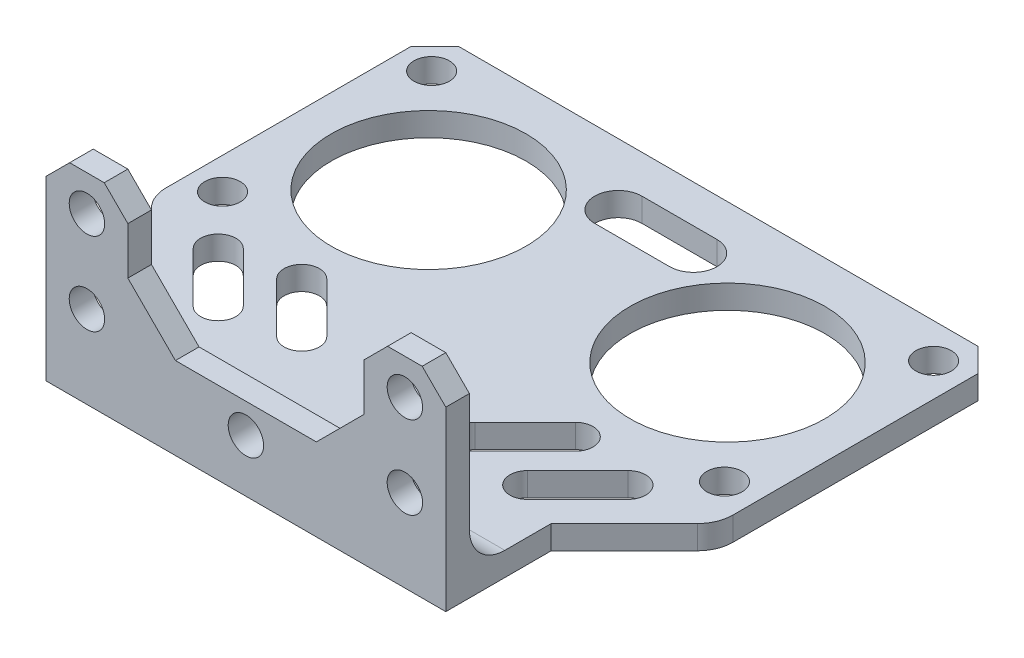
SolidWorks part; units mm, degrees
ref_plane "Front" through (0, 0, 0) normal (0, 0, 1) x (1, 0, 0)
ref_plane "Top" through (0, 0, 0) normal (0, 1, 0) x (1, 0, 0)
ref_plane "Right" through (0, 0, 0) normal (1, 0, 0) x (0, 0, -1)
sketch "Sketch1" plane through (0, 0, 0) normal (0, 1, 0) x (1, 0, 0)
  line L0 (-24, -12) -> (-16.9289, -19.0711)
  line L2 (-24, -12) -> (-24, 12)
  line L3 (-24, 12) -> (24, 12)
  line L4 (24, -12) -> (24, 12)
  line L5 (-24, -12) -> (24, 12) construction
  line L6 (-24, 12) -> (24, -12) construction
  line L7 (0, -12) -> (0, -28) construction
  line L8 (-16.9289, -19.0711) -> (-16.9289, -28)
  line L9 (-16.9289, -28) -> (16.9289, -28)
  line L10 (16.9289, -19.0711) -> (16.9289, -28)
  line L11 (24, -12) -> (16.9289, -19.0711)
  point P0 (0, 0)
  dimension "D1" = 48
  dimension "D2" = 24
  dimension "D4" = 10
  dimension "D5" = 16
extrude "Boss-Extrude1" add sketch "Sketch1" along normal blind 2
sketch "Sketch2" plane through (0, 2, 0) normal (0, 1, 0) x (1, 0, 0)
  line L0 (16.9289, -28) -> (16.9289, -19.0711) construction
  line L1 (-16.9289, -28) -> (16.9289, -28)
  line L2 (-16.9289, -28) -> (-16.9289, -26)
  line L3 (-16.9289, -26) -> (16.9289, -26)
  line L4 (16.9289, -28) -> (16.9289, -26)
  dimension "D1" = 2
extrude "Boss-Extrude2" add sketch "Sketch2" along normal blind 15
sketch "Sketch4" plane through (0, 2, 0) normal (0, 1, 0) x (1, 0, 0)
  circle A0 centre (-21.3236, -8.6566) radius 1.5
  circle A1 centre (-21.3236, 9.0534) radius 1.5
  circle A2 centre (21.1864, 9.0534) radius 1.5
  circle A3 centre (21.1864, -8.6566) radius 1.5
  dimension "D1" = 3
extrude "Cut-Extrude5" cut sketch "Sketch4" against normal blind 10
sketch "Sketch5" plane through (0, 0, 0) normal (0, -1, 0) x (-1, 0, 0)
  line L0 (-3.1114, 8.7834) -> (3.2486, 8.7834)
  line L1 (-3.1114, 4.7834) -> (3.2486, 4.7834)
  circle A0 centre (-12.5864, 0.1984) radius 8.25
  circle A1 centre (12.7236, 0.1984) radius 8.25
  arc A2 (-3.1114, 8.7834) -> (-3.1114, 4.7834) centre (-3.1114, 6.7834) ccw
  arc A3 (3.2486, 4.7834) -> (3.2486, 8.7834) centre (3.2486, 6.7834) ccw
  dimension "D1" = 16.5
extrude "Cut-Extrude6" cut sketch "Sketch5" against normal blind 10
sketch "Sketch6" plane through (0, 0, 0) normal (0, -1, 0) x (-1, 0, 0)
  line L0 (-17.347, -12.9962) -> (-13.1043, -17.2388) construction
  line L5 (-16.2863, -11.9355) -> (-12.0437, -16.1782)
  line L6 (-18.4076, -14.0569) -> (-14.165, -18.2995)
  line L7 (-11.5835, -11.6885) -> (-7.3409, -15.9312) construction
  line L8 (-10.5229, -10.6279) -> (-6.2802, -14.8705)
  line L9 (-12.6442, -12.7492) -> (-8.4016, -16.9918)
  line L10 (-16.9289, -19.0711) -> (-24, -12) construction
  line L11 (0, -28) -> (0, 12) construction
  line L12 (16.9289, -28) -> (-16.9289, -28) construction
  line L13 (-24, 12) -> (24, 12) construction
  line L14 (11.5835, -11.6885) -> (7.3409, -15.9312) construction
  line L15 (10.5229, -10.6279) -> (6.2802, -14.8705)
  line L16 (12.6442, -12.7492) -> (8.4016, -16.9918)
  line L17 (17.347, -12.9962) -> (13.1043, -17.2388) construction
  line L18 (16.2863, -11.9355) -> (12.0437, -16.1782)
  line L19 (18.4076, -14.0569) -> (14.165, -18.2995)
  line L20 (-11, -23.1923) -> (11, -23.1923) construction
  line L21 (-11, -21.1923) -> (11, -21.1923)
  line L22 (-11, -25.1923) -> (11, -25.1923)
  arc A2 (-16.2863, -11.9355) -> (-18.4076, -14.0569) centre (-17.347, -12.9962) ccw
  arc A3 (-14.165, -18.2995) -> (-12.0437, -16.1782) centre (-13.1043, -17.2388) ccw
  arc A4 (-10.5229, -10.6279) -> (-12.6442, -12.7492) centre (-11.5835, -11.6885) ccw
  arc A5 (-8.4016, -16.9918) -> (-6.2802, -14.8705) centre (-7.3409, -15.9312) ccw
  arc A6 (10.5229, -10.6279) -> (12.6442, -12.7492) centre (11.5835, -11.6885) cw
  arc A7 (8.4016, -16.9918) -> (6.2802, -14.8705) centre (7.3409, -15.9312) cw
  arc A8 (16.2863, -11.9355) -> (18.4076, -14.0569) centre (17.347, -12.9962) cw
  arc A9 (14.165, -18.2995) -> (12.0437, -16.1782) centre (13.1043, -17.2388) cw
  arc A10 (-11, -21.1923) -> (-11, -25.1923) centre (-11, -23.1923) ccw
  arc A11 (11, -25.1923) -> (11, -21.1923) centre (11, -23.1923) ccw
  point P2 (-15.2256, -15.1175)
  point P7 (-9.4622, -13.8099)
  point P24 (9.4622, -13.8099)
  point P31 (15.2256, -15.1175)
  point P38 (0, -23.1923)
  dimension "D1" = 3
  dimension "D2" = 6
  dimension "D3" = 2
  dimension "D4" = 4
  dimension "D5" = 4
  dimension "D6" = 22
extrude "Cut-Extrude7" cut sketch "Sketch6" against normal through all
sketch "Sketch7" plane through (0, 0, 26) normal (0, 0, -1) x (-1, 0, 0)
  line L0 (16.9289, 17) -> (9.997, 17)
  line L1 (-16.9289, 17) -> (16.9289, 17) construction
  line L2 (9.997, 17) -> (9.997, 11)
  line L3 (9.997, 11) -> (5.9676, 6.9706)
  line L4 (0, 17) -> (0, 5.7697) construction
  line L5 (5.9676, 6.9706) -> (-5.9676, 6.9706)
  line L6 (-9.997, 17) -> (-9.997, 11)
  line L7 (-9.997, 11) -> (-5.9676, 6.9706)
  line L8 (9.997, 17) -> (-9.997, 17)
  line L9 (13.463, 17) -> (13.463, 7.7079) construction
  circle A0 centre (13.463, 14) radius 1.5
  circle A1 centre (13.463, 7) radius 1.5
  circle A2 centre (-13.463, 14) radius 1.5
  circle A3 centre (-13.463, 7) radius 1.5
  circle A4 centre (0, 4.4706) radius 1.5
  point P14 (0, 6.9706)
  line M13 (16.9289, 17) -> (-16.9289, 17)
  dimension "D2" = 3
  dimension "D5" = 2.5
  dimension "D1" = 6
  dimension "D3" = 3
  dimension "D4" = 7
extrude "Cut-Extrude8" cut sketch "Sketch7" against normal through all contours L6 L7 L5 L3 L2 M13 | A4 | A3 | A2 | A1 | A0 region at (0, 12.3088, 26) region at (-13.463, 14, 26) region at (-13.463, 7, 26) region at (13.463, 14, 26) region at (13.463, 7, 26) region at (0, 4.4706, 26)
fillet "Fillet1" radius 3 1 edges at (0, 2, 26)
chamfer "Chamfer1" distance 2 angle 45 6 edges at (-16.9289, 17, 27) (16.9289, 17, 27) (-24, 1, -12) (24, 1, -12) (9.997, 17, 27) (-9.997, 17, 27)
fillet "Fillet2" radius 3 2 edges at (-24, 1, 12) (24, 1, 12)
